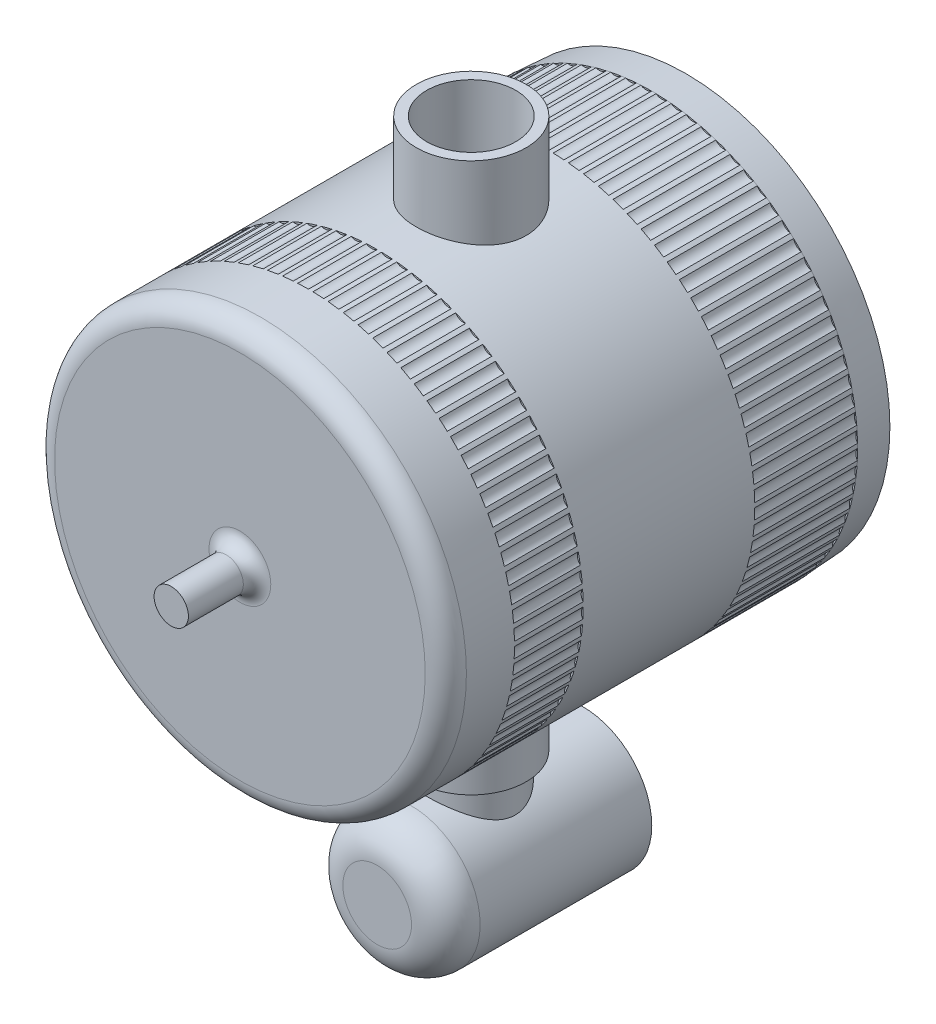
SolidWorks part; units mm, degrees
ref_plane "Front Plane" through (0, 0, 0) normal (0, 0, 1) x (1, 0, 0)
ref_plane "Top Plane" through (0, 0, 0) normal (0, 1, 0) x (1, 0, 0)
ref_plane "Right Plane" through (0, 0, 0) normal (1, 0, 0) x (0, 0, -1)
sketch "Sketch1" plane through (0, 0, 0) normal (0, 0, 1) x (1, 0, 0)
  line L0 (0, 29.0411) -> (0, -19.9015) construction
  circle A0 centre (0, 0) radius 15
  arc A1 (0.3159, 14.9967) -> (1.1032, 14.9594) centre (0.737, 15.5576) ccw
  arc A2 (1.4226, 14.9324) -> (2.2049, 14.8371) centre (1.8839, 15.4607) ccw
  arc A3 (2.5215, 14.7866) -> (3.2947, 14.6337) centre (3.0206, 15.2794) ccw
  arc A4 (3.6066, 14.56) -> (4.3664, 14.3504) centre (4.1408, 15.0146) ccw
  arc A5 (4.6721, 14.2538) -> (5.4143, 13.9888) centre (5.2383, 14.6677) ccw
  arc A6 (5.712, 13.8699) -> (6.4326, 13.5507) centre (6.3073, 14.2408) ccw
  arc A7 (6.7207, 13.4101) -> (7.4158, 13.0386) centre (7.3418, 13.7361) ccw
  arc A8 (7.6927, 12.8772) -> (8.3585, 12.4553) centre (8.3362, 13.1564) ccw
  arc A9 (8.6227, 12.2739) -> (9.2555, 11.804) centre (9.2851, 12.5048) ccw
  arc A10 (9.5056, 11.6036) -> (10.102, 11.0883) centre (10.1832, 11.785) ccw
  arc A11 (10.3366, 10.8699) -> (10.8933, 10.3119) centre (11.0258, 11.0007) ccw
  arc A12 (11.1112, 10.0768) -> (11.6251, 9.4793) centre (11.8081, 10.1564) ccw
  arc A13 (11.825, 9.2287) -> (12.2935, 8.5948) centre (12.5259, 9.2566) ccw
  arc A14 (12.4743, 8.3302) -> (12.8946, 7.6634) centre (13.1753, 8.3063) ccw
  arc A15 (13.0554, 7.3862) -> (13.4254, 6.6902) centre (13.7528, 7.3105) ccw
  arc A16 (13.5653, 6.4018) -> (13.8828, 5.6805) centre (14.2551, 6.2749) ccw
  arc A17 (14.001, 5.3825) -> (14.2644, 4.6397) centre (14.6796, 5.205) ccw
  arc A18 (14.3603, 4.3338) -> (14.5681, 3.5735) centre (15.0239, 4.1067) ccw
  arc A19 (14.6411, 3.2614) -> (14.7922, 2.4879) centre (15.2862, 2.9859) ccw
  arc A20 (14.842, 2.1712) -> (14.9356, 1.3886) centre (15.465, 1.8488) ccw
  arc A21 (14.9618, 1.0692) -> (14.9974, 0.2818) centre (15.5593, 0.7016) ccw
  arc A22 (15, -0.0387) -> (14.9772, -0.8265) centre (15.5686, -0.4494) ccw
  arc A23 (14.9561, -1.1464) -> (14.8753, -1.9304) centre (15.4929, -1.5979) ccw
  arc A24 (14.8306, -2.2478) -> (14.6921, -3.0237) centre (15.3326, -2.7378) ccw
  arc A25 (14.6241, -3.337) -> (14.4287, -4.1005) centre (15.0885, -3.8626) ccw
  arc A26 (14.3377, -4.4079) -> (14.0864, -5.1549) centre (14.762, -4.9664) ccw
  arc A27 (13.973, -5.4547) -> (13.6672, -6.1811) centre (14.3549, -6.0431) ccw
  arc A28 (13.532, -6.4718) -> (13.1734, -7.1736) centre (13.8695, -7.0867) ccw
  arc A29 (13.0171, -7.4535) -> (12.6077, -8.1269) centre (13.3082, -8.0916) ccw
  arc A30 (12.4311, -8.3945) -> (11.973, -9.0358) centre (12.6743, -9.0524) ccw
  arc A31 (11.7772, -9.2896) -> (11.273, -9.8954) centre (11.9711, -9.9637) ccw
  arc A32 (11.059, -10.134) -> (10.5114, -10.7009) centre (11.2026, -10.8206) ccw
  arc A33 (10.2804, -10.9231) -> (9.6925, -11.448) centre (10.3729, -11.6184) ccw
  arc A34 (9.4456, -11.6525) -> (8.8205, -12.1325) centre (9.4865, -12.3527) ccw
  arc A35 (8.5593, -12.3182) -> (7.9004, -12.7508) centre (8.5483, -13.0196) ccw
  arc A36 (7.6262, -12.9167) -> (6.9372, -13.2995) centre (7.5634, -13.6153) ccw
  arc A37 (6.6514, -13.4447) -> (5.936, -13.7755) centre (6.5373, -14.1367) ccw
  arc A38 (5.6403, -13.8992) -> (4.9025, -14.1762) centre (5.4754, -14.5809) ccw
  arc A39 (4.5984, -14.2778) -> (3.8421, -14.4996) centre (4.3836, -14.9455) ccw
  arc A40 (3.5314, -14.5784) -> (2.7608, -14.7437) centre (3.2678, -15.2284) ccw
  arc A41 (2.4451, -14.7994) -> (1.6644, -14.9074) centre (2.1343, -15.4282) ccw
  arc A42 (1.3455, -14.9395) -> (0.5589, -14.9896) centre (0.989, -15.5436) ccw
  arc A43 (0.2385, -14.9981) -> (-0.5496, -14.9899) centre (-0.1616, -15.5742) ccw
  arc A44 (-0.8698, -14.9748) -> (-1.6552, -14.9084) centre (-1.3114, -15.5198) ccw
  arc A45 (-1.9734, -14.8696) -> (-2.7517, -14.7454) centre (-2.454, -15.3805) ccw
  arc A46 (-3.0661, -14.6833) -> (-3.8332, -14.502) centre (-3.5831, -15.1573) ccw
  arc A47 (-4.1422, -14.4167) -> (-4.8937, -14.1793) centre (-4.6928, -14.8513) ccw
  arc A48 (-5.1956, -14.0715) -> (-5.9275, -13.7791) centre (-5.7768, -14.4642) ccw
  arc A49 (-6.2206, -13.6493) -> (-6.929, -13.3037) centre (-6.8292, -13.998) ccw
  arc A50 (-7.2116, -13.1526) -> (-7.8925, -12.7557) centre (-7.8443, -13.4555) ccw
  arc A51 (-8.1633, -12.5841) -> (-8.813, -12.138) centre (-8.8166, -12.8394) ccw
  arc A52 (-9.0704, -11.9469) -> (-9.6854, -11.454) centre (-9.7408, -12.1532) ccw
  arc A53 (-9.9279, -11.2444) -> (-10.5048, -10.7074) centre (-10.6117, -11.4006) ccw
  arc A54 (-10.7312, -10.4805) -> (-11.2669, -9.9023) centre (-11.4247, -10.5858) ccw
  arc A55 (-11.4759, -9.6593) -> (-11.9675, -9.0432) centre (-12.1753, -9.7131) ccw
  arc A56 (-12.158, -8.7854) -> (-12.6027, -8.1347) centre (-12.8594, -8.7874) ccw
  arc A57 (-12.7736, -7.8635) -> (-13.169, -7.1817) centre (-13.4733, -7.8137) ccw
  arc A58 (-13.3195, -6.8987) -> (-13.6634, -6.1896) centre (-14.0135, -6.7974) ccw
  arc A59 (-13.7926, -5.8962) -> (-14.0832, -5.1636) centre (-14.4773, -5.7439) ccw
  arc A60 (-14.1904, -4.8615) -> (-14.4261, -4.1094) centre (-14.8619, -4.659) ccw
  arc A61 (-14.5106, -3.8002) -> (-14.6902, -3.0328) centre (-15.1654, -3.5487) ccw
  arc A62 (-14.7517, -2.7182) -> (-14.8741, -1.9396) centre (-15.3861, -2.419) ccw
  arc A63 (-14.9121, -1.6213) -> (-14.9767, -0.8358) centre (-15.5227, -1.2761) ccw
  arc A64 (-14.9911, -0.5156) -> (-14.9975, 0.2726) centre (-15.5746, -0.1262) ccw
  arc A65 (-14.9883, 0.593) -> (-14.9364, 1.3794) centre (-15.5414, 1.0244) ccw
  arc A66 (-14.9036, 1.6983) -> (-14.7938, 2.4787) centre (-15.4233, 2.1693) ccw
  arc A67 (-14.7374, 2.7943) -> (-14.5703, 3.5645) centre (-15.2209, 3.3024) ccw
  arc A68 (-14.4908, 3.8751) -> (-14.2673, 4.6309) centre (-14.9355, 4.4175) ccw
  arc A69 (-14.1651, 4.9347) -> (-13.8863, 5.6719) centre (-14.5684, 5.5085) ccw
  arc A70 (-13.7619, 5.9673) -> (-13.4295, 6.6819) centre (-14.1218, 6.5694) ccw
  arc A71 (-13.2837, 6.9674) -> (-12.8994, 7.6555) centre (-13.5981, 7.5944) ccw
  arc A72 (-12.7328, 7.9294) -> (-12.2988, 8.5872) centre (-13.0001, 8.5779) ccw
  arc A73 (-12.1125, 8.8481) -> (-11.631, 9.4721) centre (-12.3311, 9.5145) ccw
  arc A74 (-11.4259, 9.7184) -> (-10.8997, 10.3052) centre (-11.5948, 10.3992) ccw
  arc A75 (-10.677, 10.5357) -> (-10.1089, 11.082) centre (-10.7951, 11.2271) ccw
  arc A76 (-9.8697, 11.2955) -> (-9.2628, 11.7983) centre (-9.9365, 11.9937) ccw
  arc A77 (-9.0086, 11.9936) -> (-8.3662, 12.4502) centre (-9.0236, 12.6948) ccw
  arc A78 (-8.0982, 12.6261) -> (-7.4239, 13.034) centre (-8.0614, 13.3266) ccw
  arc A79 (-7.1437, 13.1897) -> (-6.441, 13.5467) centre (-7.0552, 13.8855) ccw
  arc A80 (-6.15, 13.6813) -> (-5.4229, 13.9854) centre (-6.0104, 14.3686) ccw
  arc A81 (-5.1229, 14.0981) -> (-4.3753, 14.3477) centre (-4.9328, 14.7733) ccw
  arc A82 (-4.0677, 14.4379) -> (-3.3037, 14.6317) centre (-3.8283, 15.0972) ccw
  arc A83 (-2.9903, 14.6989) -> (-2.2141, 14.8357) centre (-2.7029, 15.3388) ccw
  arc A84 (-1.8966, 14.8796) -> (-1.1124, 14.9587) centre (-1.5627, 15.4965) ccw
  arc A85 (-0.7925, 14.979) -> (-0.0046, 15) centre (-0.414, 15.5696) ccw
  point P263 (0, 0)
  dimension "D1" = 30
  dimension "D2" = 85
extrude "Boss-Extrude1" add sketch "Sketch1" along normal blind 30 contours L0 A0 A85 A84 A83 A82 A81 A80 A79 A78 A77 A76 A75 A74 A73 A72 A71 A70 A69 A68 A67 A66 A65 A64 A63 A62 A61 | A0 L0 A43 A42 A41 A40 A39 A38 A37 A36 A35 A34 A33 A32 A31 A30 A29 A28 A27 A26 A25 A24 A23 A22 A21 A20 A19 region at (6.34, 0, 0) region at (-6.3407, 0, 0)
sketch "Sketch2" plane through (0, 0, 0) normal (0, 0, -1) x (-1, 0, 0)
  circle A0 centre (0, 0) radius 15
  circle A1 centre (0, 0) radius 14.6606
extrude "Boss-Extrude2" add sketch "Sketch2" along normal blind 2.5 draft 3.5 separate body contours A0 A1 region at (14.9576, 0, 0)
sketch "Sketch3" plane through (0, 0, 30) normal (0, 0, 1) x (1, 0, 0)
  circle A0 centre (0, 0) radius 15
extrude "Boss-Extrude3" add sketch "Sketch3" against normal blind 5
extrude "Boss-Extrude4" add sketch "Sketch3<2>" against normal blind 12.5 from offset 10 offset against normal yes
sketch "Sketch3<2>" plane through (0, 0, 30) normal (0, 0, 1) x (1, 0, 0) same geometry as "Sketch3"
sketch "Sketch4" plane through (0, 0, 0) normal (0, 1, 0) x (1, 0, 0)
  line L0 (0, 12.224) -> (0, -38.5199) construction
  circle A0 centre (0, -13.148) radius 3.245
  circle A1 centre (0, -13.148) radius 4
  dimension "D1" = 6.49
  dimension "D2" = 8
extrude "Boss-Extrude5" add sketch "Sketch4" along normal blind 20 and the other way blind 20
sketch "Sketch5" plane through (0, -20, 0) normal (0, -1, 0) x (1, 0, 0)
  circle A0 centre (0, 13.148) radius 3.2
extrude "Boss-Extrude6" add sketch "Sketch5" along normal blind 2.5 separate body
sketch "Sketch7" plane through (0, 0, 30) normal (0, 0, 1) x (1, 0, 0)
  circle A0 centre (0, -26.3419) radius 5
  dimension "D1" = 10
extrude "Boss-Extrude7" add sketch "Sketch7" along normal blind 15 from offset 25 offset against normal yes
sketch "Sketch8" plane through (0, 0, 5) normal (0, 0, -1) x (-1, 0, 0)
  circle A0 centre (0, -26.3419) radius 4.25
  dimension "D1" = 8.5
extrude "Cut-Extrude1" cut sketch "Sketch8" against normal blind 2.5 draft 10
fillet "Fillet2" radius 2.5 1 edges at (5, -26.3419, 20)
fillet "Fillet3" radius 1.5 1 edges at (15, 0, 30)
sketch "Sketch9" plane through (0, 0, 30) normal (0, 0, 1) x (1, 0, 0)
  circle A0 centre (0, 0) radius 1.25
  dimension "D1" = 2.5
extrude "Boss-Extrude8" add sketch "Sketch9" along normal blind 5
fillet "Fillet4" radius 1 1 edges at (1.25, 0, 30)
